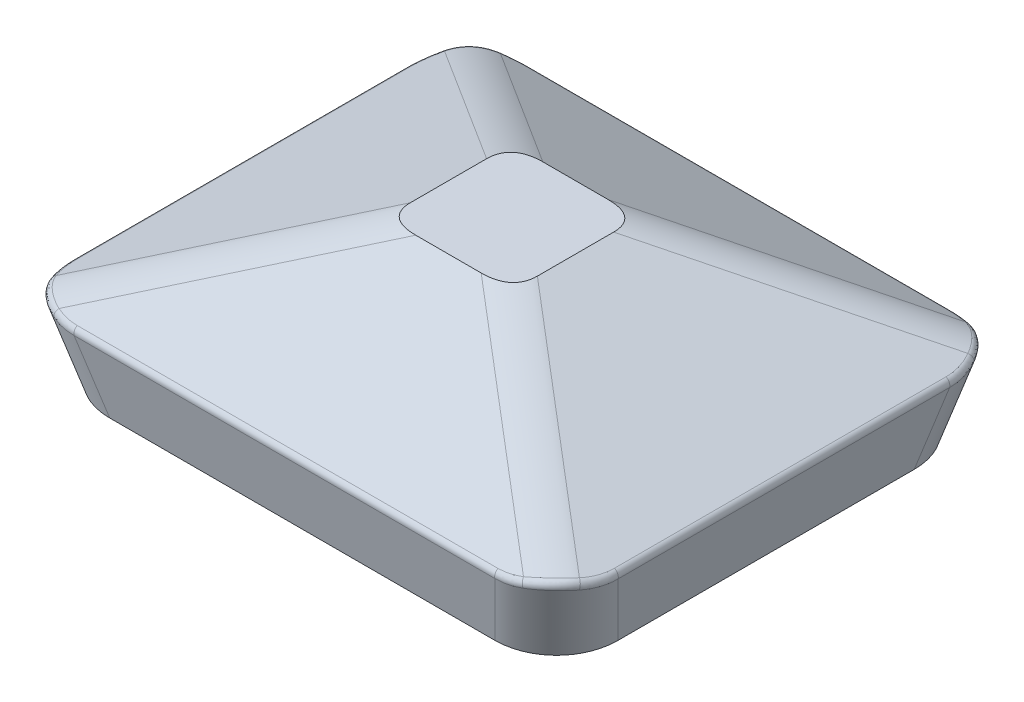
SolidWorks part; units mm, degrees
material "ABS"
ref_plane "Front Plane" through (0, 0, 0) normal (0, 0, 1) x (1, 0, 0)
ref_plane "Top Plane" through (0, 0, 0) normal (0, 1, 0) x (1, 0, 0)
ref_plane "Right Plane" through (0, 0, 0) normal (1, 0, 0) x (0, 0, -1)
sketch "Sketch2" plane through (0, 0, 0) normal (0, 0, 1) x (1, 0, 0)
  line L0 (40, 0) -> (-40, 0)
  line L1 (-40, 0) -> (-43, 12)
  line L2 (-43, 12) -> (-10, 26)
  line L3 (-10, 26) -> (10, 26)
  line L4 (0, 0) -> (0, 26) construction
  line L5 (-43, 12) -> (0, 12) construction
  line L6 (43, 12) -> (10, 26)
  line L7 (40, 0) -> (43, 12)
  dimension "D1" = 12
  dimension "D2" = 14
  dimension "D3" = 43
  dimension "D4" = 40
  dimension "D5" = 10
extrude "Boss-Extrude1" add sketch "Sketch2" along normal blind 72
sketch "Sketch3" plane through (0, 0, 0) normal (1, 0, 0) x (0, 0, -1)
  line L0 (-36, 26) -> (-36, 0) construction
  line L1 (-72, 26) -> (0, 26) construction
  line L2 (-72, 0) -> (0, 0) construction
  line L3 (-3, 0) -> (-69, 0)
  line L4 (-69, 0) -> (-72, 12)
  line L5 (-72, 0) -> (-72, 12) construction
  line L6 (-72, 12) -> (-46, 26)
  line L7 (-46, 26) -> (-26, 26)
  line L8 (-72, 12) -> (-36, 12) construction
  line L9 (0, 12) -> (-26, 26)
  line L10 (-3, 0) -> (0, 12)
  dimension "D1" = 10
  dimension "D2" = 33
  dimension "D3" = 12
extrude "Cut-Extrude1" cut sketch "Sketch3" against normal through all and the other way through all flip side to cut
fillet "Fillet1" radius 10 8 edges at (26.5, 19, 59) (41.5, 6, 70.5) (-26.5, 19, 59) (-41.5, 6, 70.5) (41.5, 6, 1.5) (26.5, 19, 13) (-26.5, 19, 13) (-41.5, 6, 1.5)
fillet "Fillet2" radius 1 16 edges at (42.7258, 12.1163, 7.2125) (40.559, 12.71, 2.8251) (35.3136, 12.0936, 0.1738) (0, 12, 0) (-35.3136, 12.0936, 0.1738) (-40.559, 12.71, 2.8251) (-42.7258, 12.1163, 7.2125) (-43, 12, 36) (-42.7258, 12.1163, 64.7875) (-39.481, 12.683, 70.1413) (-35.3136, 12.0936, 71.8262) (0, 12, 72) (35.3136, 12.0936, 71.8262) (40.559, 12.71, 69.1749) (42.7258, 12.1163, 64.7875) (43, 12, 36)
